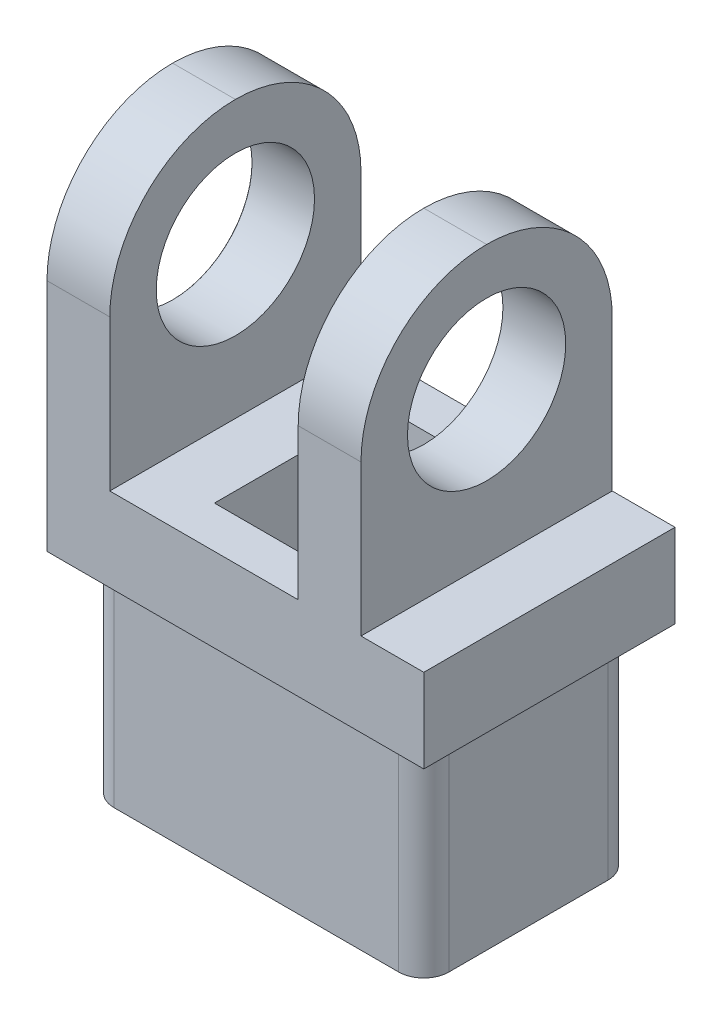
SolidWorks part; units mm, degrees
ref_plane "Front Plane" through (0, 0, 0) normal (0, 0, 1) x (1, 0, 0)
ref_plane "Top Plane" through (0, 0, 0) normal (0, 1, 0) x (1, 0, 0)
ref_plane "Right Plane" through (0, 0, 0) normal (1, 0, 0) x (0, 0, -1)
sketch "Sketch2" plane through (0, 0, 0) normal (0, 1, 0) x (1, 0, 0)
  line L1 (0, 0) -> (28.575, 0)
  line L2 (0, 0) -> (0, 19.05)
  line L3 (0, 19.05) -> (28.575, 19.05)
  line L4 (28.575, 0) -> (28.575, 19.05)
  line L5 (0, 19.05) -> (4.7625, 19.05)
  line L6 (0, 19.05) -> (0, 0)
  line L7 (0, 0) -> (4.7625, 0)
  line L8 (4.7625, 19.05) -> (4.7625, 0)
  line L9 (19.05, 19.05) -> (23.8125, 19.05)
  line L10 (19.05, 19.05) -> (19.05, 0)
  line L11 (19.05, 0) -> (23.8125, 0)
  line L12 (23.8125, 19.05) -> (23.8125, 0)
  dimension "D1" = 19.05
  dimension "D2" = 28.575
  dimension "D3" = 4.7625
  dimension "D4" = 4.7625
  dimension "D5" = 4.7625
extrude "Boss-Extrude1" add sketch "Sketch2" along normal blind 20.955 contours L8 L3 L2 L1 | L12 L3 L10 L1 region at (2.3813, 0, -9.525) region at (21.4312, 0, -9.525)
sketch "Sketch3" plane through (0, 0, 0) normal (0, 1, 0) x (1, 0, 0)
  line L0 (19.05, 0) -> (23.8125, 0) construction
  line L1 (1.5875, 17.4625) -> (26.9875, 17.4625)
  line L2 (1.5875, 17.4625) -> (1.5875, 1.5875)
  line L3 (1.5875, 1.5875) -> (26.9875, 1.5875)
  line L4 (26.9875, 17.4625) -> (26.9875, 1.5875)
  line L5 (19.05, 19.05) -> (23.8125, 19.05) construction
  line L10 (0, 0) -> (0, 19.05) construction
  dimension "D1" = 25.4
  dimension "D2" = 15.875
  dimension "D3" = 1.5875
  dimension "D4" = 1.5875
  dimension "D5" = 1.5875
extrude "Boss-Extrude2" add sketch "Sketch3" against normal blind 22.225
extrude "Boss-Extrude3" add sketch "Sketch2<3>" against normal blind 6.35 contours L10 L3 L8 L1 | L3 L12 L1 L4 | L8 L3 L2 L1 | L12 L3 L10 L1 region at (2.3813, 0, -9.525) region at (11.9062, 0, -9.525) region at (21.4312, 0, -9.525) region at (26.1937, 0, -9.525)
sketch "Sketch2<3>" plane through (0, 0, 0) normal (0, 1, 0) x (1, 0, 0) same geometry as "Sketch2"
fillet "Fillet1" radius 9.525 4 edges at (2.3813, 20.955, -19.05) (2.3813, 20.955, 0) (21.4312, 20.955, 0) (21.4312, 20.955, -19.05)
hole_wizard "Ø12.0mm Dowel Hole1" positions "3DSketch2" profile "Sketch4" hole size "Ø12.0" standard "ANSI Metric" end condition through all
sketch3d "3DSketch2"
  line L0 (0, 11.43, -19.05) -> (0, -6.35, -19.05) construction
  line L1 (0, 11.43, 0) -> (0, -6.35, 0) construction
  point P0 (0, 11.43, -9.525)
  point P5 (0, 0, 0)
  dimension "D1" = 9.525
  dimension "D2" = 9.525
  dimension "D3" = 9.525
sketch "Sketch4" plane through (0, 11.43, -9.525) normal (0, 1, 0) x (0, 0, 1)
  line L0 (0, 0) -> (0, 28.575)
  line L1 (0, 28.575) -> (6, 28.575)
  line L2 (6, 28.575) -> (6, 0.025)
  line L3 (6, 0.025) -> (6.025, 0)
  line L5 (6.025, 0) -> (0, 0)
  line L6 (-6, 0.025) -> (-6.025, 0) construction
  line L11 (0, -6.35) -> (0, 107.95) construction
  dimension "Thru Hole Dia." = 12
  dimension "Thru Hole Depth" = 28.575
  dimension "Near C'Sink Dia." = 12.05
  dimension "Near C'Sink Angle" = 90
fillet "Fillet2" radius 1.905 4 edges at (1.5875, -14.2875, -17.4625) (1.5875, -14.2875, -1.5875) (26.9875, -14.2875, -1.5875) (26.9875, -14.2875, -17.4625)
sketch "Sketch5" plane through (0, 0, 0) normal (0, 1, 0) x (1, 0, 0)
  line L0 (19.05, 9.525) -> (19.05, 0) construction
  line L1 (9.525, 15.875) -> (19.05, 15.875)
  line L2 (9.525, 15.875) -> (9.525, 3.175)
  line L3 (9.525, 3.175) -> (19.05, 3.175)
  line L4 (19.05, 15.875) -> (19.05, 3.175)
  line L5 (4.7625, 19.05) -> (19.05, 19.05) construction
  line L6 (4.7625, 0) -> (19.05, 0) construction
  line L7 (4.7625, 19.05) -> (4.7625, 0) construction
  dimension "D1" = 3.175
  dimension "D2" = 3.175
  dimension "D3" = 4.7625
extrude "Cut-Extrude1" cut sketch "Sketch5" against normal through all
